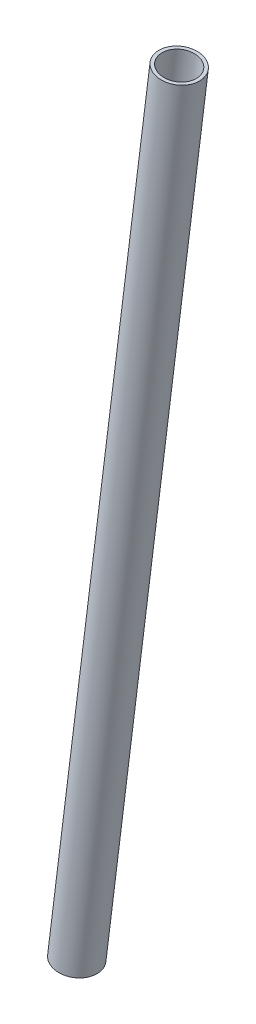
SolidWorks part; units mm, degrees
ref_plane "Front Plane" through (0, 0, 0) normal (0, 0, 1) x (1, 0, 0)
ref_plane "Top Plane" through (0, 0, 0) normal (0, 1, 0) x (1, 0, 0)
ref_plane "Right Plane" through (0, 0, 0) normal (1, 0, 0) x (0, 0, -1)
sketch3d "3DSketch1"
  line L0 (567.75, 180, 43) -> (616.52, 525.27, 49.7) construction
  line L1 (567.75, 180, 43) -> (616.52, 525.27, 49.7) construction
  line L2 (573.9728, 224.0545, 43.8549) -> (610.2972, 481.2155, 48.8451)
  dimension "D1" = 44.5
  dimension "D2" = 44.5
sweep "Sweep-Thin1" add path "3DSketch1" circular profile diameter 12.7 parameters "D1"=1, "D3"=12.7
